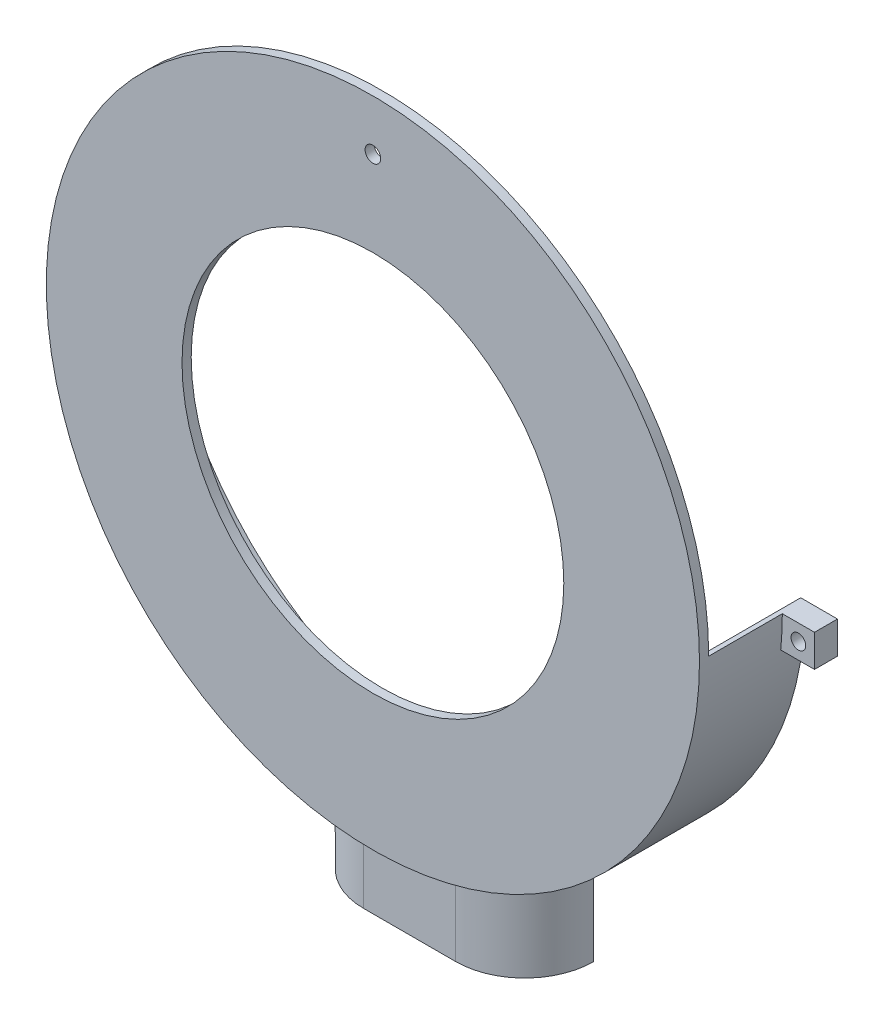
SolidWorks part; units mm, degrees
ref_plane "Front Plane" through (0, 0, 0) normal (0, 0, 1) x (1, 0, 0)
ref_plane "Top Plane" through (0, 0, 0) normal (0, 1, 0) x (1, 0, 0)
ref_plane "Right Plane" through (0, 0, 0) normal (1, 0, 0) x (0, 0, -1)
sketch "Sketch1" plane through (0, 0, 0) normal (0, 0, 1) x (1, 0, 0)
  line L0 (-71, 0) -> (71, 0)
  circle A0 centre (0, 0) radius 71
  circle A1 centre (0, 0) radius 70
  point P7 (0, 0)
extrude "Boss-Extrude1" add sketch "Sketch1" along normal blind 21 contours A1 L0 A0 region at (70.5, -1.5876, 0)
sketch "Sketch2" plane through (0, 0, 21) normal (0, 0, 1) x (1, 0, 0)
  line L0 (-80, 0) -> (80, 0)
  circle A0 centre (0, 0) radius 80
  circle A1 centre (0, 0) radius 41.5
  circle A2 centre (0, 0) radius 71
  point P7 (0, 0)
  arc M1 (70, 0) -> (-70, 0) centre (0, 0) cw
  line M2 (-70, 0) -> (-71, 0)
  arc M3 (-71, 0) -> (71, 0) centre (0, 0) ccw
  line M4 (71, 0) -> (70, 0)
extrude "Boss-Extrude2" add sketch "Sketch2" along normal blind 2 contours M4 M1 M2 M3 | A1 L0 M1 | A2 | A1 region at (-70.5, -1.5876, 21) region at (-55.75, -1.5652, 21)
sketch "Sketch3" plane through (0, 0, 0) normal (0, 0, -1) x (-1, 0, 0)
  line L0 (-25, -71) -> (25, -71)
  line L1 (25, -71) -> (25, -66.453)
  line L2 (-25, -71) -> (-25, -66.453)
  line L3 (-25, -71) -> (-25, -91)
  line L4 (-25, -91) -> (25, -91)
  line L5 (25, -91) -> (25, -71)
  arc A0 (-71, 0) -> (71, 0) centre (0, 0) ccw construction
  arc A1 (-71, 0) -> (71, 0) centre (0, 0) ccw
  point P6 (0, -71)
  arc M5 (-71, 0) -> (71, 0) centre (0, 0) ccw
extrude "Boss-Extrude3" add sketch "Sketch3" against normal blind 15 contours L2 L0 M5 | L0 L1 M5 | L4 L5 L0 L3 region at (18.7907, -69.6437, 0) region at (0, -81, 0) region at (-18.7907, -69.6437, 0)
sketch "Sketch8" plane through (0, 0, 0) normal (0, 0, -1) x (-1, 0, 0)
  line L0 (-78, -7) -> (-72.2291, -7)
  line L1 (-71, 0) -> (-78, 0)
  line L3 (-73, -7) -> (-78, -7)
  line L4 (-78, 0) -> (-78, -7)
  line L6 (-71, 0) -> (-78, -7) construction
  line L7 (-73, -7) -> (-69.6491, -7)
  line L8 (-69.6491, -7) -> (-71, 0)
  line L9 (0, -70) -> (0, 0) construction
  line L10 (71, 0) -> (78, -7) construction
  line L11 (69.6491, -7) -> (71, 0)
  line L12 (73, -7) -> (69.6491, -7)
  line L13 (78, 0) -> (78, -7)
  line L14 (73, -7) -> (78, -7)
  line L15 (71, 0) -> (78, 0)
  line L16 (78, -7) -> (72.2291, -7)
  circle A0 centre (-74.5, -3.5) radius 1.6
  arc A1 (-70, 0) -> (70, 0) centre (0, 0) ccw construction
  circle A2 centre (74.5, -3.5) radius 1.6
  dimension "D1" = 7
  dimension "D2" = 7
extrude "Boss-Extrude5" add sketch "Sketch8" against normal blind 5 contours L11 L6 A0 L0 | L6 L1 L4 A0 | L0 L11 | L14 L12 L11 L15 L13 | A2 region at (77.891, -3.5, 0)
fillet "Fillet2" radius 15 2 edges at (-25, -78.7265, 15) (25, -78.7265, 15)
sketch "Sketch11" plane through (0, -91, 0) normal (0, -1, 0) x (1, 0, 0)
  line L0 (10, 12) -> (-10, 12)
  line L1 (-21.619, 3) -> (21.619, 3)
  line L2 (10, 15) -> (-10, 15)
  line L3 (-25, 0) -> (25, 0)
  line L4 (10, 15) -> (-10, 15)
  line L5 (-25, 0) -> (25, 0)
  line L6 (21.619, 3) -> (21.619, 0)
  line L7 (-21.619, 3) -> (-21.619, 0)
  arc A0 (-10, 12) -> (-21.619, 3) centre (-10, 0) ccw
  arc A1 (21.619, 3) -> (10, 12) centre (10, 0) ccw
  arc A2 (-10, 15) -> (-25, 0) centre (-10, 0) ccw
  arc A3 (25, 0) -> (10, 15) centre (10, 0) ccw
  arc A4 (-10, 15) -> (-25, 0) centre (-10, 0) ccw
  arc A5 (25, 0) -> (10, 15) centre (10, 0) ccw
  dimension "D1" = 0
  dimension "D2" = 3
extrude "Cut-Extrude7" cut sketch "Sketch11" against normal blind 20 contours L1 L7 L5 L6 | L1 A1 L0 A0 region at (0, -91, 7.1524) region at (0, -91, 1.5)
sketch "Sketch12" plane through (0, 0, 23) normal (0, 0, 1) x (1, 0, 0)
  circle A0 centre (0, 0) radius 60
  circle A1 centre (0, 60) radius 1.7
extrude "Cut-Extrude8" cut sketch "Sketch12" against normal blind 10 contours A1
